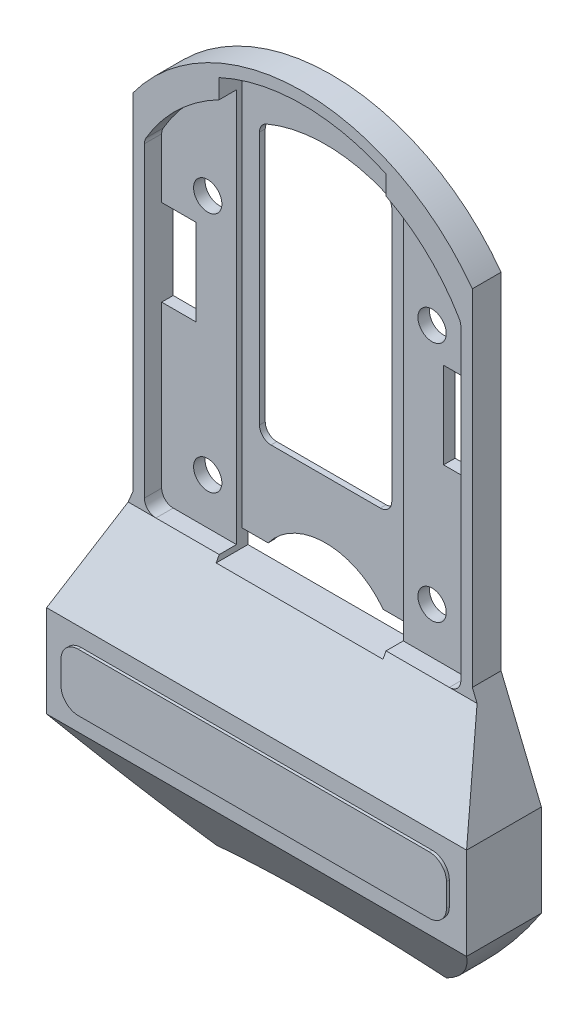
SolidWorks part; units mm, degrees
material "PA Type 6"
ref_plane "Front Plane" through (0, 0, 0) normal (0, 0, 1) x (1, 0, 0)
ref_plane "Top Plane" through (0, 0, 0) normal (0, 1, 0) x (1, 0, 0)
ref_plane "Right Plane" through (0, 0, 0) normal (1, 0, 0) x (0, 0, -1)
sketch "Sketch1" plane through (0, 0, 0) normal (0, 0, 1) x (1, 0, 0)
  line L1 (-29.5, 21.5083) -> (-29.5, -38.4917)
  line L2 (0, 90.0503) -> (0, -130.8543) construction
  line L4 (-11.5, 22.5922) -> (-11.5, -21.4917)
  line L5 (-9.5, -23.4917) -> (9.5, -23.4917)
  line L6 (11.5, 22.5922) -> (11.5, -21.4917)
  line L7 (27.5, 14.8523) -> (27.5, -38.4917)
  line L8 (-20, -89.4917) -> (20, -89.4917)
  line L9 (29.5, 21.5083) -> (29.5, -38.4917)
  line L11 (-27.5, 14.8523) -> (-27.5, -38.4917)
  line L15 (-27.5, 20.8465) -> (-27.5, -87.4917) construction
  line L16 (14.5, 31.3141) -> (14.5, 27.9755)
  line L17 (27.5, 20.8465) -> (27.5, -87.4917) construction
  line L18 (-14.5, 31.3141) -> (-14.5, 27.9755)
  line L19 (27.5, 4.5083) -> (21.5, 4.5083)
  line L20 (21.5, 4.5083) -> (21.5, -10.4917)
  line L21 (21.5, -10.4917) -> (27.5, -10.4917)
  line L22 (-21.5, -10.4917) -> (-27.5, -10.4917)
  line L23 (-27.5, 4.5083) -> (-21.5, 4.5083)
  line L24 (-21.5, 4.5083) -> (-21.5, -10.4917)
  line L25 (-14.5, -38.4917) -> (-10, -38.4917)
  line L26 (10, -38.4917) -> (14.5, -38.4917)
  line L27 (-29.5, -38.4917) -> (-36.5, -55.4917)
  line L28 (-36.5, -55.4917) -> (-36.5, -71.4917)
  line L29 (29.5, -38.4917) -> (36.5, -55.4917)
  line L30 (-27.5, -87.4917) -> (27.5, -87.4917) construction
  line L31 (36.5, -55.4917) -> (36.5, -71.4917)
  line L32 (-29.5, -89.4917) -> (29.5, -89.4917) construction
  line L33 (29.5, 21.5083) -> (29.5, -89.4917) construction
  line L34 (-29.5, 21.5083) -> (-29.5, -89.4917) construction
  line L35 (14.5, -41.4917) -> (14.5, 27.9755)
  line L36 (-14.5, -41.4917) -> (14.5, -41.4917)
  line L37 (-14.5, -41.4917) -> (-14.5, 27.9755)
  line L38 (25.5, -40.4917) -> (14.5, -40.4917)
  line L39 (-14.5, -40.4917) -> (-25.5, -40.4917)
  line L40 (25.5, -40.4917) -> (30.3235, -40.4917)
  line L41 (-25.5, -40.4917) -> (-30.3235, -40.4917)
  arc A0 (-29.5, 21.5083) -> (29.5, 21.5083) centre (0, 0) cw
  arc A1 (-10.2752, 24.4359) -> (10.2752, 24.4359) centre (0, 0) cw
  arc A2 (11.5, -21.4917) -> (9.5, -23.4917) centre (9.5, -21.4917) cw
  arc A3 (-11.5, -21.4917) -> (-9.5, -23.4917) centre (-9.5, -21.4917) ccw
  arc A4 (10.2752, 24.4359) -> (11.5, 22.5922) centre (9.5, 22.5922) cw
  arc A5 (-11.5, 22.5922) -> (-10.2752, 24.4359) centre (-9.5, 22.5922) cw
  arc A6 (-14.5, 31.3141) -> (14.5, 31.3141) centre (0, 0) cw
  arc A8 (-27.5, 20.8465) -> (27.5, 20.8465) centre (0, 0) cw construction
  arc A9 (-14.5, 27.9755) -> (-27.2282, 15.8589) centre (0, 0) ccw
  arc A10 (14.5, 27.9755) -> (27.2282, 15.8589) centre (0, 0) cw
  arc A11 (27.2282, 15.8589) -> (27.5, 14.8523) centre (25.5, 14.8523) cw
  arc A12 (-27.2282, 15.8589) -> (-27.5, 14.8523) centre (-25.5, 14.8523) ccw
  arc A13 (-10, -38.4917) -> (10, -38.4917) centre (0, -45.9917) cw
  arc A14 (-20, -89.4917) -> (-36.5, -71.4917) centre (27.7928, -29.1191) cw
  arc A15 (-20, -89.4917) -> (20, -89.4917) centre (0, -166.9513) cw
  arc A16 (20, -89.4917) -> (36.5, -71.4917) centre (-27.7928, -29.1191) ccw
  arc A17 (27.5, -38.4917) -> (25.5, -40.4917) centre (25.5, -38.4917) cw
  arc A18 (-27.5, -38.4917) -> (-25.5, -40.4917) centre (-25.5, -38.4917) ccw
  point P12 (0, -23.4917)
  point P14 (0, 23.8839)
  point P18 (11.5, -23.4917)
  point P21 (-11.5, -23.4917)
  point P24 (11.5, 23.8839)
  point P27 (-11.5, 23.8839)
  point P30 (0, -89.4917)
  point P53 (27.5, 15.3828)
  point P56 (-27.5, 15.3828)
  point P62 (0, -33.4917)
  dimension "D5" = 10
  dimension "D7" = 2
  dimension "D9" = 2
  dimension "D2" = 36.5083
  dimension "D12" = 32
  dimension "D10" = 31.51
  dimension "D16" = 2
  dimension "D24" = 77
  dimension "D22" = 18
  dimension "D27" = 2
  dimension "D28" = 80
  dimension "D1" = 59
  dimension "D3" = 126
  dimension "D4" = 11.5
  dimension "D6" = 50
  dimension "D8" = 11.5
  dimension "D11" = 3
  dimension "D13" = 15
  dimension "D14" = 6
  dimension "D15" = 15
  dimension "D17" = 20
  dimension "D18" = 10
  dimension "D19" = 17
  dimension "D20" = 7
  dimension "D21" = 40
  dimension "D23" = 3
  dimension "D25" = 3
  dimension "D26" = 3
extrude "Boss-Extrude1" add sketch "Sketch1" along normal blind 1 contours L25 A13 L26 L35 L16 A6 L18 L37 L4 A5 A1 A4 L6 A2 L5 A3 region at (-13.7145, -5.2581, 0)
extrude "Boss-Extrude2" add sketch "Sketch1<3>" along normal blind 2 contours L11 A18 L39 L37 A9 A12 L23 L24 L22 | A17 L7 L21 L20 L19 A11 A10 L35 L38 region at (-20.3295, -9.3511, 0) region at (20.3295, -9.3511, 0)
sketch "Sketch1<3>" plane through (0, 0, 0) normal (0, 0, 1) x (1, 0, 0) same geometry as "Sketch1"
extrude "Boss-Extrude3" add sketch "Sketch1<5>" along normal blind 5 contours A18 L11 A12 A9 L18 A6 L16 A10 A11 L7 A17 L40 L29 L9 A0 L1 L27 L41 region at (0, 35.5282, 0)
sketch "Sketch1<5>" plane through (0, 0, 0) normal (0, 0, 1) x (1, 0, 0) same geometry as "Sketch1"
extrude "Boss-Extrude4" add sketch "Sketch1<6>" along normal blind 13 contours A15 A16 L31 L29 L40 L38 L35 L36 L37 L39 L41 L27 L28 A14 region at (0, -63.6826, 0)
sketch "Sketch1<6>" plane through (0, 0, 0) normal (0, 0, 1) x (1, 0, 0) same geometry as "Sketch1"
sketch "Sketch2" plane through (0, 0, 0) normal (1, 0, 0) x (0, 0, -1)
  line L0 (-5, -40.4917) -> (-13, -55.4917)
  line L1 (-5, -40.4917) -> (-13, -40.4917)
  line L2 (-13, -40.4917) -> (-13, -55.4917)
  line L3 (-13, -71.4917) -> (0, -89.4917)
  line L4 (0, -89.4917) -> (-13, -89.4917)
  line L5 (-13, -89.4917) -> (-13, -71.4917)
extrude "Cut-Extrude1" cut sketch "Sketch2" against normal up to next and the other way up to next
sketch "Sketch3" plane through (0, 0, 13) normal (0, 0, 1) x (1, 0, 0)
  line L8 (-33.5, -58.4917) -> (-33.5, -68.4917)
  line L9 (-33.5, -68.4917) -> (33.5, -68.4917)
  line L10 (33.5, -68.4917) -> (33.5, -58.4917)
  line L11 (33.5, -58.4917) -> (-33.5, -58.4917)
  line L12 (-33.5, -61.4917) -> (-33.5, -65.4917)
  line L13 (-30.5, -68.4917) -> (30.5, -68.4917)
  line L14 (33.5, -65.4917) -> (33.5, -61.4917)
  line L15 (30.5, -58.4917) -> (-30.5, -58.4917)
  arc A0 (30.5, -68.4917) -> (33.5, -65.4917) centre (30.5, -65.4917) ccw
  arc A1 (33.5, -61.4917) -> (30.5, -58.4917) centre (30.5, -61.4917) ccw
  arc A2 (-33.5, -65.4917) -> (-30.5, -68.4917) centre (-30.5, -65.4917) ccw
  arc A3 (-33.5, -61.4917) -> (-30.5, -58.4917) centre (-30.5, -61.4917) cw
  dimension "D2" = 3
  dimension "D1" = 3
extrude "Boss-Extrude5" add sketch "Sketch3" along normal blind 0.5
hole_wizard "#10 (0.1935) Diameter Hole1" positions "Sketch6" profile "Sketch7" hole size "#10" standard "ANSI Inch" end condition through all
sketch "Sketch6" plane through (0, 0, 2) normal (0, 0, 1) x (1, 0, 0)
  line L0 (25.5, -40.4917) -> (14.5, -40.4917) construction
  line L1 (27.5, -10.4917) -> (27.5, -38.4917) construction
  line L2 (-25.5, -40.4917) -> (-14.5, -40.4917) construction
  line L3 (-27.5, 14.8523) -> (-27.5, -38.4917) construction
  point P0 (19.5, -32.4917)
  point P2 (-19.5, -32.4917)
  point P4 (-19.5, 9.5083)
  point P6 (19.5, 9.5083)
  dimension "D1" = 8
  dimension "D2" = 8
  dimension "D3" = 8
  dimension "D4" = 8
  dimension "D5" = 42
  dimension "D6" = 42
sketch "Sketch7" plane through (19.5, -32.4917, 2) normal (1, 0, 0) x (0, -1, 0)
  line L0 (0, 0) -> (0, 2)
  line L1 (0, 2) -> (2.4574, 2)
  line L2 (2.4574, 2) -> (2.4574, 0)
  line L5 (2.4574, 0) -> (0, 0)
  line L11 (0, -6.35) -> (0, 107.95) construction
  dimension "Thru Hole Dia." = 4.9149
  dimension "Thru Hole Depth" = 2
